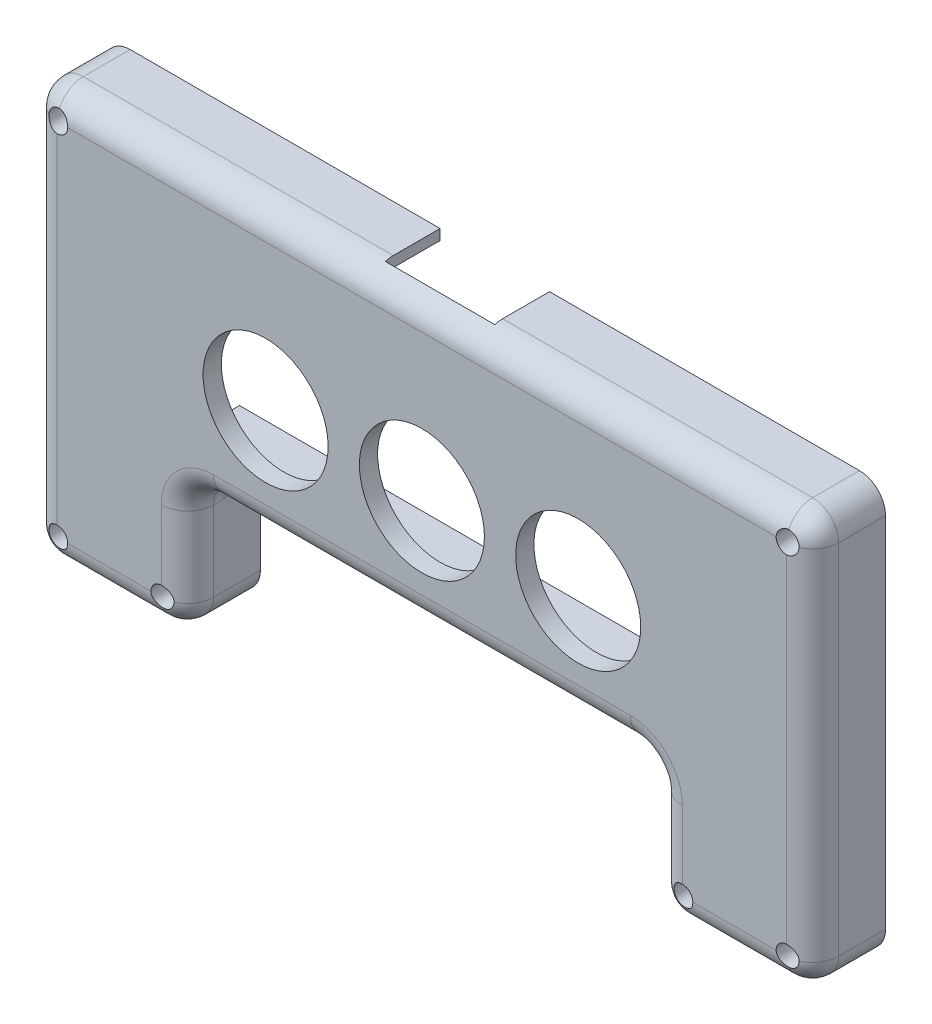
SolidWorks part; units mm, degrees
ref_plane "Front Plane" through (0, 0, 0) normal (0, 0, 1) x (1, 0, 0)
ref_plane "Top Plane" through (0, 0, 0) normal (0, 1, 0) x (1, 0, 0)
ref_plane "Right Plane" through (0, 0, 0) normal (1, 0, 0) x (0, 0, -1)
sketch "Sketch1" plane through (0, 0, 0) normal (0, 0, 1) x (1, 0, 0)
  line L0 (-43.2313, -10.6035) -> (43.7687, -10.6035)
  line L1 (0.2687, 39.3965) -> (70.2687, 39.3965)
  line L2 (-74.7313, 34.3965) -> (-74.7313, -34.6652)
  line L3 (-69.7313, -39.6652) -> (-49.7313, -39.6652)
  line L4 (75.2687, 34.3965) -> (75.2687, -34.3447)
  line L5 (70.2687, -39.3447) -> (50.2687, -39.3447)
  line L6 (-44.7313, -34.6652) -> (-44.7313, -12.1035)
  line L7 (45.2687, -34.3447) -> (45.2687, -12.1035)
  line L8 (-43.2313, -10.6035) -> (-43.2313, 24.3965)
  line L9 (-36.2313, 27.3965) -> (-36.2313, 37.3965)
  line L10 (-36.2313, 37.3965) -> (-10.2313, 37.3965)
  line L11 (-10.2313, 37.3965) -> (-10.2313, 39.3965)
  line L12 (-43.2313, 24.3965) -> (43.7687, 24.3965)
  line L13 (-69.7313, 39.3965) -> (0.2687, 39.3965)
  line L14 (36.7687, 24.3965) -> (36.7687, 36.3965)
  line L15 (36.7687, 36.3965) -> (10.7687, 36.3965)
  line L16 (10.7687, 36.3965) -> (10.7687, 39.3965)
  line L17 (43.7687, 24.3965) -> (43.7687, -10.6035)
  line L18 (-36.2313, 27.3965) -> (-36.2313, 24.3965)
  circle A0 centre (-69.7313, 34.3965) radius 2
  circle A1 centre (-69.7313, -34.6652) radius 2
  circle A2 centre (-49.7313, -34.6652) radius 2
  arc A3 (50.2687, -39.3447) -> (45.2687, -34.3447) centre (50.2687, -34.3447) cw
  arc A4 (-49.7313, -39.6652) -> (-44.7313, -34.6652) centre (-49.7313, -34.6652) ccw
  arc A5 (-69.7313, -39.6652) -> (-74.7313, -34.6652) centre (-69.7313, -34.6652) cw
  arc A6 (70.2687, -39.3447) -> (75.2687, -34.3447) centre (70.2687, -34.3447) ccw
  arc A7 (75.2687, 34.3965) -> (70.2687, 39.3965) centre (70.2687, 34.3965) ccw
  arc A8 (-74.7313, 34.3965) -> (-69.7313, 39.3965) centre (-69.7313, 34.3965) cw
  arc A9 (45.2687, -12.1035) -> (43.7687, -10.6035) centre (43.7687, -12.1035) ccw
  arc A10 (-43.2313, -10.6035) -> (-44.7313, -12.1035) centre (-43.2313, -12.1035) ccw
  circle A11 centre (50.2687, -34.3447) radius 2
  circle A12 centre (70.2687, -34.3447) radius 2
  circle A13 centre (70.2687, 34.3965) radius 2
  circle A20 centre (50.2687, -34.3447) radius 1.25
  circle A21 centre (70.2687, -34.3447) radius 1.25
  circle A22 centre (70.2687, 34.3965) radius 1.25
  circle A23 centre (-49.7313, -34.6652) radius 1.25
  circle A24 centre (-69.7313, -34.6652) radius 1.25
  circle A25 centre (-69.7313, 34.3965) radius 1.25
  circle A26 centre (-29.7313, 6.3965) radius 12
  circle A27 centre (0.2687, 6.3965) radius 12
  circle A28 centre (30.2687, 6.3965) radius 12
extrude "Boss-Extrude1" add sketch "Sketch1" along normal blind 7 contours A10 L8 L12 L9 L10 L11 L13 A8 L2 A5 L3 A4 L6 A2 A1 A0 | L17 A28 L12 L8 A26 L0 A27 | L15 L16 L1 L13 L11 L10 L9 L12 L14 | A9 L7 A3 L5 A6 L4 A7 L1 L16 L15 L14 L12 L17 A13 A12 A11 region at (-42.2935, 6.8965, 0) region at (-57.6193, 2.646, 0) region at (57.8005, 3.1464, 0) region at (-0.3644, 31.0613, 0)
extrude "Boss-Extrude2" add sketch "Sketch1<8>" along normal blind 3.5 contours A28 | A27 | A26 region at (-29.7313, 6.3965, 0) region at (0.2687, 6.3965, 0) region at (30.2687, 6.3965, 0)
sketch "Sketch1<8>" plane through (0, 0, 0) normal (0, 0, 1) x (1, 0, 0) same geometry as "Sketch1"
extrude "Cut-Extrude12" cut sketch "Sketch1<9>" along normal blind 3.5 contours L15 L16 L1 L13 L11 L10 L9 L12 L14 | L17 A28 L12 L8 A26 L0 A27 | A28 | A27 | A26 region at (-42.2935, 6.8965, 0) region at (-0.3644, 31.0613, 0) region at (-29.7313, 6.3965, 0) region at (0.2687, 6.3965, 0) region at (30.2687, 6.3965, 0)
sketch "Sketch1<9>" plane through (0, 0, 0) normal (0, 0, 1) x (1, 0, 0) same geometry as "Sketch1"
extrude "Boss-Extrude3" add sketch "Sketch1<11>" along normal blind 3.5 contours A11 A20 | A12 A21 region at (48.3253, -34.3447, 0) region at (68.3253, -34.3447, 0)
sketch "Sketch1<11>" plane through (0, 0, 0) normal (0, 0, 1) x (1, 0, 0) same geometry as "Sketch1"
extrude "Boss-Extrude4" add sketch "Sketch1<13>" along normal blind 3.5 contours A0 A25 region at (-71.6747, 34.3965, 0)
sketch "Sketch1<13>" plane through (0, 0, 0) normal (0, 0, 1) x (1, 0, 0) same geometry as "Sketch1"
extrude "Boss-Extrude5" add sketch "Sketch1<15>" along normal blind 3.5 contours A13 A22 region at (68.3253, 34.3965, 0)
sketch "Sketch1<15>" plane through (0, 0, 0) normal (0, 0, 1) x (1, 0, 0) same geometry as "Sketch1"
extrude "Boss-Extrude6" add sketch "Sketch1<16>" along normal blind 3.5 contours A2 A23 | A1 A24 region at (-71.6747, -34.6652, 0) region at (-51.6747, -34.6652, 0)
sketch "Sketch1<16>" plane through (0, 0, 0) normal (0, 0, 1) x (1, 0, 0) same geometry as "Sketch1"
sketch "Sketch5" plane through (-44.7313, 0, 0) normal (1, 0, 0) x (0, 0, -1)
  line L0 (-7, -34.6652) -> (-7, -9.2932)
  line L1 (-7, -34.6652) -> (0, -34.6652)
  line L2 (-7, -34.6652) -> (0, -34.6652) construction
  line L3 (0, -34.6652) -> (0, -9.2932)
  line L4 (0, -9.2932) -> (-7, -9.2932)
  line L5 (-7, -9.2932) -> (-7, -14.2932)
  line L6 (0, -14.2932) -> (0, -9.2932)
  line L7 (-7, -14.2932) -> (0, -14.2932)
  line M2 (0, -12.1035) -> (-7, -12.1035)
  line M3 (-7, -12.1035) -> (-7, -34.6652)
extrude "Boss-Extrude11" add sketch "Sketch5" along normal blind 90.1 contours L7 L3 M3 M2 | L3 L4 L0 M2 region at (-44.7313, -13.1983, 3.5) region at (-44.7313, -10.6983, 3.5)
fillet "Fillet4" radius 5 10 edges at (0.2687, 39.3965, 7) (75.2687, 0.0259, 7) (-74.7313, -0.1344, 7) (60.2687, -39.3447, 7) (-59.7313, -39.6652, 7) (45.2687, -24.3189, 7) (-44.7313, -24.4792, 7) (0.2687, -14.2932, 7) (45.2687, -14.2932, 3.5) (-44.7313, -14.2932, 3.5)
extrude "Boss-Extrude12" add sketch "Sketch1<17>" against normal blind 3 contours A9 L7 A3 L5 A6 L4 A7 L1 L16 L15 L14 L12 L17 A13 A12 A11 | A10 L8 L12 L18 L9 L10 L11 L13 A8 L2 A5 L3 A4 L6 A2 A1 A0 region at (-57.6193, 2.646, 0) region at (57.8005, 3.1464, 0)
sketch "Sketch1<17>" plane through (0, 0, 0) normal (0, 0, 1) x (1, 0, 0) same geometry as "Sketch1"
sketch "Sketch6" plane through (0, 0, 0) normal (0, 0, -1) x (-1, 0, 0)
  line L0 (43.2313, -9.2932) -> (-43.7687, -9.2932)
  line L1 (-43.7687, -9.2932) -> (43.2313, -9.2932) construction
  line L2 (-43.7687, -9.2932) -> (-43.7687, -10.6035)
  line L3 (-45.2687, -12.1035) -> (-45.2687, -19.2932)
  line L4 (-45.2687, -19.2932) -> (-45.2687, -12.1035) construction
  line L5 (-40.2687, -14.2932) -> (39.7313, -14.2932)
  line L6 (43.2313, -9.2932) -> (43.2313, -10.6035)
  line L7 (44.7313, -12.1035) -> (44.7313, -19.2932)
  arc A1 (-40.2687, -14.2932) -> (-45.2687, -19.2932) centre (-40.2687, -19.2932) ccw construction
  spline S0 degree 3 poles (-43.7687, -10.6035) (-44.4758, -10.5968) (-45.1755, -11.0592) (-45.2687, -12.1035) knots 0 0 0 0 1 1 1 1
  spline S1 degree 3 poles (-45.2687, -19.2932) (-45.0857, -15.9269) (-42.6233, -14.4004) (-40.2687, -14.2932) knots 0 0 0 0 1 1 1 1
  spline S2 degree 3 poles (44.7313, -12.1035) (44.7296, -11.3964) (44.2684, -10.6859) (43.2313, -10.6035) knots 0 0 0 0 1 1 1 1
  spline S3 degree 3 poles (44.7313, -19.2932) (44.7219, -16.9362) (43.1842, -14.5753) (39.7313, -14.2932) knots 0 0 0 0 1 1 1 1
extrude "Boss-Extrude14" add sketch "Sketch6" along normal blind 3
extrude "Boss-Extrude15" add sketch "Sketch1<18>" along normal blind 3 contours A12 A21 | A11 A20 | A13 A22 | A0 A25 | A2 A23 | A1 A24 region at (-71.6747, 34.3965, 0) region at (-71.6747, -34.6652, 0) region at (-51.6747, -34.6652, 0) region at (48.3253, -34.3447, 0) region at (68.3253, -34.3447, 0) region at (68.3253, 34.3965, 0)
sketch "Sketch1<18>" plane through (0, 0, 0) normal (0, 0, 1) x (1, 0, 0) same geometry as "Sketch1"
extrude "Boss-Extrude17" add sketch "Sketch1<20>" against normal blind 3 contours A12 A21 region at (68.3253, -34.3447, 0)
sketch "Sketch1<20>" plane through (0, 0, 0) normal (0, 0, 1) x (1, 0, 0) same geometry as "Sketch1"
extrude "Boss-Extrude18" add sketch "Sketch1<21>" against normal blind 3 contours A11 A20 | A2 A23 | A1 A24 | A0 A25 | A13 A22 region at (-71.6747, 34.3965, 0) region at (-71.6747, -34.6652, 0) region at (-51.6747, -34.6652, 0) region at (48.3253, -34.3447, 0) region at (68.3253, 34.3965, 0)
sketch "Sketch1<21>" plane through (0, 0, 0) normal (0, 0, 1) x (1, 0, 0) same geometry as "Sketch1"
sketch "Sketch7" plane through (0, 0, -3) normal (0, 0, -1) x (-1, 0, 0)
  line L0 (-43.7687, -9.2932) -> (-49.2975, -9.2932)
  line L1 (-49.2975, -9.2932) -> (-49.2975, -28.0932)
  line L2 (-49.2975, -28.0932) -> (-67.2975, -28.0932)
  line L3 (-67.2975, -28.0932) -> (-67.2975, 29.0573)
  line L4 (-67.2975, 29.0573) -> (-63.6612, 29.0573)
  line L5 (-63.6612, 29.0573) -> (-63.6612, 36.6295)
  line L6 (-63.6612, 36.6295) -> (-36.7687, 36.3965)
  line L7 (43.2313, -9.2932) -> (48.7513, -9.2932)
  line L8 (43.2313, -9.2932) -> (43.2313, 24.3965) construction
  line L9 (48.7513, -9.2932) -> (48.7513, -28.0932)
  line L10 (48.7513, -28.0932) -> (66.7134, -28.0932)
  line L11 (66.7134, -28.0932) -> (66.7134, 29.0573)
  line L12 (66.7134, 29.0573) -> (63.9496, 29.0573)
  line L13 (63.9496, 29.0573) -> (63.9496, 36.3965)
  line L14 (36.2313, 37.3965) -> (63.9496, 37.3965)
  line L15 (-43.7687, -9.2932) -> (-43.7687, 24.3965)
  line L16 (-43.7687, 24.3965) -> (-36.7687, 24.3965)
  line L17 (-36.7687, 24.3965) -> (-36.7687, 36.3965)
  line L18 (43.2313, -9.2932) -> (43.2313, 24.3965)
  line L19 (43.2313, 24.3965) -> (36.2313, 24.3965)
  line L20 (43.2313, 24.3965) -> (36.2313, 24.3965) construction
  line L21 (36.2313, 24.3965) -> (36.2313, 37.3965)
  line L22 (63.9496, 37.3965) -> (63.9496, 36.3965)
extrude "Cut-Extrude13" cut sketch "Sketch7" against normal blind 7
extrude "Boss-Extrude19" add sketch "Sketch1<22>" against normal blind 7 contours A10 L8 L12 L18 L9 L10 L11 L13 A8 L2 A5 L3 A4 L6 A2 A1 A0 | A9 L7 A3 L5 A6 L4 A7 L1 L16 L15 L14 L12 L17 A13 A12 A11 region at (-57.6193, 2.646, 0) region at (57.8005, 3.1464, 0)
sketch "Sketch1<22>" plane through (0, 0, 0) normal (0, 0, 1) x (1, 0, 0) same geometry as "Sketch1"
extrude "Cut-Extrude16" cut sketch "Sketch7<4>" against normal blind 7
sketch "Sketch7<4>" plane through (0, 0, -3) normal (0, 0, -1) x (-1, 0, 0) same geometry as "Sketch7"
extrude "Cut-Extrude17" cut sketch "Sketch7<5>" along normal blind 7
sketch "Sketch7<5>" plane through (0, 0, -3) normal (0, 0, -1) x (-1, 0, 0) same geometry as "Sketch7"
extrude "Boss-Extrude20" add sketch "Sketch6<2>" along normal blind 7
sketch "Sketch6<2>" plane through (0, 0, 0) normal (0, 0, -1) x (-1, 0, 0) same geometry as "Sketch6"
